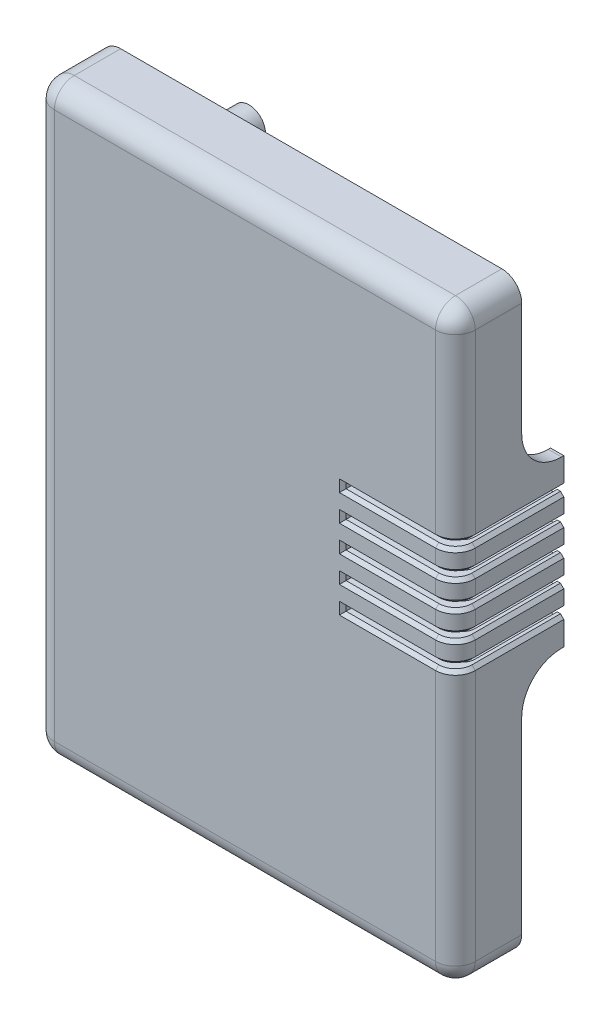
SolidWorks part; units mm, degrees
ref_plane "Front Plane" through (0, 0, 0) normal (0, 0, 1) x (1, 0, 0)
ref_plane "Top Plane" through (0, 0, 0) normal (0, 1, 0) x (1, 0, 0)
ref_plane "Right Plane" through (0, 0, 0) normal (1, 0, 0) x (0, 0, -1)
ref_plane "Plane1" through (0, 0, 8) normal (0, 0, 1) x (1, 0, 0)
sketch "Sketch2" plane through (0, 0, 8) normal (0, 0, 1) x (1, 0, 0)
  line L1 (-23.6788, 60.2968) -> (39.8212, 60.2968)
  line L2 (-23.6788, 60.2968) -> (-23.6788, -28.2032)
  line L3 (-23.6788, -28.2032) -> (39.8212, -28.2032)
  line L4 (39.8212, 60.2968) -> (39.8212, -28.2032)
extrude "Boss-Extrude1" add sketch "Sketch2" along normal blind 2
sketch "Sketch3" plane through (0, 0, 8) normal (0, 0, -1) x (-1, 0, 0)
  line L4 (23.6788, -28.2032) -> (23.6788, 60.2968)
  line L5 (23.6788, 60.2968) -> (-39.8212, 60.2968)
  line L6 (-39.8212, 60.2968) -> (-39.8212, -28.2032)
  line L7 (-39.8212, -28.2032) -> (23.6788, -28.2032)
  line L8 (23.6788, -28.2032) -> (23.6788, 60.2968)
  line L9 (23.6788, 60.2968) -> (-39.8212, 60.2968)
  line L10 (-37.8212, -26.2032) -> (-39.8212, -26.2032)
  line L11 (-39.8212, -28.2032) -> (23.6788, -28.2032)
  line L12 (-39.8212, -28.2032) -> (-39.8212, 60.2968) construction
  line L13 (-39.8212, -26.2032) -> (-39.8212, -28.2032)
  line L14 (-37.8212, 58.2968) -> (-39.8212, 58.2968)
  line L15 (-39.8212, 58.2968) -> (-39.8212, 60.2968)
  line L16 (21.6788, -26.2032) -> (21.6788, 58.2968)
  line L17 (21.6788, 58.2968) -> (-37.8212, 58.2968)
  line L18 (-37.8212, 58.2968) -> (-37.8212, -26.2032)
  line L19 (-37.8212, -26.2032) -> (21.6788, -26.2032)
  line L20 (21.6788, -26.2032) -> (21.6788, 58.2968)
  line L21 (21.6788, 58.2968) -> (-37.8212, 58.2968)
  line L23 (-37.8212, -26.2032) -> (21.6788, -26.2032)
  dimension "D1" = 0
  dimension "D2" = 2
extrude "Boss-Extrude2" add sketch "Sketch3" along normal up to surface (8 mm away) up to face at (-23.6788, 16.0468, 9)
sketch "Sketch4" plane through (39.8212, 0, 0) normal (1, 0, 0) x (0, 0, -1)
  line L0 (0, 40.207) -> (0, 57.2968) construction
  line L1 (6, 9.207) -> (6.35, 9.207) construction
  line L2 (6.35, 34.207) -> (6, 34.207) construction
  line L3 (6.35, 9.207) -> (6.35, 34.207) construction
  line L4 (0, -26.2032) -> (0, 58.2968) construction
  line L5 (0, -26.2032) -> (-8, -26.2032) construction
  line L6 (-8, -26.2032) -> (-8, 58.2968) construction
  line L7 (0, 58.2968) -> (-8, 58.2968) construction
  line L8 (0, 40.207) -> (0, 58.2968)
  line L9 (6, 9.207) -> (6.35, 9.207)
  line L10 (6.35, 34.207) -> (6, 34.207)
  line L11 (6.35, 9.207) -> (6.35, 34.207)
  line L12 (0, -26.2032) -> (0, 3.207)
  line L13 (0, -26.2032) -> (-8, -26.2032)
  line L14 (-8, -26.2032) -> (-8, 58.2968)
  line L15 (0, 58.2968) -> (-8, 58.2968)
  line L16 (0, 40.207) -> (0, 58.2968)
  arc A0 (0, 40.207) -> (6, 34.207) centre (6, 40.207) ccw construction
  arc A1 (6, 9.207) -> (0, 3.207) centre (6, 3.207) ccw construction
  arc A2 (0, 40.207) -> (6, 34.207) centre (6, 40.207) ccw
  arc A3 (6, 9.207) -> (0, 3.207) centre (6, 3.207) ccw
  line M3 (0, -26.2032) -> (-8, -26.2032)
  line M4 (-8, -26.2032) -> (-8, 58.2968)
  line M5 (-8, 58.2968) -> (0, 58.2968)
extrude "Boss-Extrude3" add sketch "Sketch4" against normal blind 2 contours A3 L9 L11 L10 A2 L8 L12 M5 M4 M3 region at (39.8212, 17.2065, 2.5632)
sketch "Sketch5" plane through (0, 0, 8) normal (0, 0, -1) x (-1, 0, 0)
  line L0 (-37.8212, -26.2032) -> (-37.8212, 58.2968) construction
  line L1 (-37.8212, 32.707) -> (-22.8212, 32.707)
  line L2 (-37.8212, 32.707) -> (-37.8212, 30.707)
  line L3 (-37.8212, 30.707) -> (-22.8212, 30.707)
  line L4 (-22.8212, 32.707) -> (-22.8212, 30.707)
  line L5 (-37.8212, 9.207) -> (-37.8212, 34.207) construction
  line L6 (-37.8212, 28.707) -> (-22.8212, 28.707)
  line L7 (-37.8212, 28.707) -> (-37.8212, 26.707)
  line L8 (-37.8212, 26.707) -> (-22.8212, 26.707)
  line L9 (-22.8212, 28.707) -> (-22.8212, 26.707)
  line L10 (-37.8212, 24.707) -> (-22.8212, 24.707)
  line L11 (-37.8212, 24.707) -> (-37.8212, 22.707)
  line L12 (-37.8212, 22.707) -> (-22.8212, 22.707)
  line L13 (-22.8212, 24.707) -> (-22.8212, 22.707)
  line L14 (-37.8212, 20.707) -> (-22.8212, 20.707)
  line L15 (-37.8212, 20.707) -> (-37.8212, 18.707)
  line L16 (-37.8212, 18.707) -> (-22.8212, 18.707)
  line L17 (-22.8212, 20.707) -> (-22.8212, 18.707)
  line L18 (-37.8212, 16.707) -> (-22.8212, 16.707)
  line L19 (-37.8212, 16.707) -> (-37.8212, 14.707)
  line L20 (-37.8212, 14.707) -> (-22.8212, 14.707)
  line L21 (-22.8212, 16.707) -> (-22.8212, 14.707)
  line L22 (-37.8212, 12.707) -> (-22.8212, 12.707)
  line L23 (-37.8212, 12.707) -> (-37.8212, 10.707)
  line L24 (-37.8212, 10.707) -> (-22.8212, 10.707)
  line L25 (-22.8212, 12.707) -> (-22.8212, 10.707)
  line L26 (-37.8212, 22.707) -> (-37.8212, 20.707) construction
  line L28 (-39.8212, 9.207) -> (-39.8212, 34.207) construction
  point P29 (-37.8212, 21.707)
  point P32 (-39.8212, 21.707)
  dimension "D1" = 15
  dimension "D2" = 2
  dimension "D3" = 2
  dimension "D4" = 2
  dimension "D5" = 2
  dimension "D6" = 2
  dimension "D7" = 2
extrude "Boss-Extrude4" add sketch "Sketch5" along normal blind 12
sketch "Sketch6" plane through (0, 0, -6.35) normal (0, 0, -1) x (-1, 0, 0)
  line L0 (-22.8212, 28.707) -> (-37.8212, 28.707) construction
  line L1 (-37.8212, 30.707) -> (-38.8212, 30.707)
  line L2 (-37.8212, 30.707) -> (-37.8212, 28.707)
  line L3 (-37.8212, 28.707) -> (-38.8212, 28.707)
  line L4 (-38.8212, 30.707) -> (-38.8212, 30.107)
  line L5 (-39.8212, 9.207) -> (-39.8212, 34.207) construction
  line L6 (-38.8212, 29.307) -> (-38.8212, 28.707)
  line L7 (-38.8212, 30.107) -> (-39.8212, 30.107)
  line L8 (-38.8212, 26.107) -> (-39.8212, 26.107)
  line L9 (-38.8212, 29.307) -> (-39.8212, 29.307)
  line L10 (-39.8212, 30.107) -> (-39.8212, 29.307)
  line L11 (-38.8212, 26.707) -> (-38.8212, 26.107)
  line L12 (-37.8212, 26.707) -> (-38.8212, 26.707)
  line L13 (-37.8212, 26.707) -> (-37.8212, 24.707)
  line L14 (-37.8212, 24.707) -> (-38.8212, 24.707)
  line L15 (-38.8212, 25.307) -> (-38.8212, 24.707)
  line L16 (-38.8212, 25.307) -> (-39.8212, 25.307)
  line L17 (-39.8212, 26.107) -> (-39.8212, 25.307)
  line L18 (-38.8212, 22.107) -> (-39.8212, 22.107)
  line L19 (-38.8212, 22.707) -> (-38.8212, 22.107)
  line L20 (-37.8212, 22.707) -> (-38.8212, 22.707)
  line L21 (-37.8212, 22.707) -> (-37.8212, 20.707)
  line L22 (-37.8212, 20.707) -> (-38.8212, 20.707)
  line L23 (-38.8212, 21.307) -> (-38.8212, 20.707)
  line L24 (-38.8212, 21.307) -> (-39.8212, 21.307)
  line L25 (-39.8212, 22.107) -> (-39.8212, 21.307)
  line L26 (-38.8212, 18.107) -> (-39.8212, 18.107)
  line L27 (-38.8212, 18.707) -> (-38.8212, 18.107)
  line L28 (-37.8212, 18.707) -> (-38.8212, 18.707)
  line L29 (-37.8212, 18.707) -> (-37.8212, 16.707)
  line L30 (-37.8212, 16.707) -> (-38.8212, 16.707)
  line L31 (-38.8212, 17.307) -> (-38.8212, 16.707)
  line L32 (-38.8212, 17.307) -> (-39.8212, 17.307)
  line L33 (-39.8212, 18.107) -> (-39.8212, 17.307)
  line L34 (-38.8212, 14.107) -> (-39.8212, 14.107)
  line L35 (-38.8212, 14.707) -> (-38.8212, 14.107)
  line L36 (-37.8212, 14.707) -> (-38.8212, 14.707)
  line L37 (-37.8212, 14.707) -> (-37.8212, 12.707)
  line L38 (-37.8212, 12.707) -> (-38.8212, 12.707)
  line L39 (-38.8212, 13.307) -> (-38.8212, 12.707)
  line L40 (-38.8212, 13.307) -> (-39.8212, 13.307)
  line L41 (-39.8212, 14.107) -> (-39.8212, 13.307)
  point P13 (-39.8212, 29.707)
  point P14 (-37.8212, 29.707)
  dimension "D1" = 1
  dimension "D2" = 0.8
  dimension "D3" = 5
extrude "Cut-Extrude1" cut sketch "Sketch6" against normal up to surface (14.35 mm away) up to face at (27.1427, 20.8984, 8)
fillet "Fillet1" radius 3 4 edges at (-23.6788, 16.0468, 10) (8.0712, -28.2032, 10) (8.0712, 60.2968, 10) (39.8212, 16.0468, 10)
fillet "Fillet2" radius 2 15 edges at (8.0712, -26.2032, 8) (37.8212, -7.7481, 8) (-21.6788, 16.0468, 8) (8.0712, 58.2968, 8) (37.8212, 45.5019, 8) (38.8212, 13.007, 8) (38.8212, 14.407, 8) (38.8212, 17.007, 8) (38.8212, 18.407, 8) (38.8212, 21.007, 8) (38.8212, 22.407, 8) (38.8212, 25.007, 8) (38.8212, 26.407, 8) (38.8212, 29.007, 8) (38.8212, 30.407, 8)
fillet "Fillet3" radius 3 8 edges at (38.9426, 59.4181, 9.1213) (-22.8001, 59.4181, 9.1213) (-22.8001, -27.3245, 9.1213) (38.9426, -27.3245, 9.1213) (39.8212, 60.2968, 3.5) (-23.6788, 60.2968, 3.5) (-23.6788, -28.2032, 3.5) (39.8212, -28.2032, 3.5)
sketch "Sketch7" plane through (0, 0, 8) normal (0, 0, -1) x (-1, 0, 0)
  line L0 (-22.8212, 30.707) -> (-22.8212, 32.707) construction
  line L1 (-39.6497, 30.107) -> (-22.8212, 30.107)
  line L2 (-39.6497, 30.107) -> (-39.6497, 29.307)
  line L3 (-39.6497, 29.307) -> (-22.8212, 29.307)
  line L4 (-22.8212, 30.107) -> (-22.8212, 29.307)
  line L5 (-39.6497, 26.107) -> (-39.6497, 25.307)
  line L6 (-39.6497, 26.107) -> (-22.8212, 26.107)
  line L7 (-39.6497, 25.307) -> (-22.8212, 25.307)
  line L8 (-22.8212, 26.107) -> (-22.8212, 25.307)
  line L9 (-39.6497, 22.107) -> (-39.6497, 21.307)
  line L10 (-39.6497, 22.107) -> (-22.8212, 22.107)
  line L11 (-39.6497, 21.307) -> (-22.8212, 21.307)
  line L12 (-22.8212, 22.107) -> (-22.8212, 21.307)
  line L13 (-39.6497, 18.107) -> (-39.6497, 17.307)
  line L14 (-39.6497, 18.107) -> (-22.8212, 18.107)
  line L15 (-39.6497, 17.307) -> (-22.8212, 17.307)
  line L16 (-22.8212, 18.107) -> (-22.8212, 17.307)
  line L17 (-39.6497, 14.107) -> (-39.6497, 13.307)
  line L18 (-39.6497, 14.107) -> (-22.8212, 14.107)
  line L19 (-39.6497, 13.307) -> (-22.8212, 13.307)
  line L20 (-22.8212, 14.107) -> (-22.8212, 13.307)
  dimension "D1" = 5
extrude "Cut-Extrude2" cut sketch "Sketch7" against normal blind 10
sketch "Sketch8" plane through (0, -28.2032, 0) normal (0, -1, 0) x (1, 0, 0)
  line L0 (-20.6788, 0) -> (36.8212, 0) construction
  line L1 (13.7903, 0) -> (-13.0098, 0)
  line L2 (13.7903, 0) -> (13.7903, 7)
  line L3 (13.7903, 7) -> (-13.0098, 7)
  line L4 (-13.0098, 0) -> (-13.0098, 7)
  line L5 (13.7903, -6.35) -> (13.7903, 0) construction
  line L6 (-13.0098, 0) -> (-13.0098, -6.35) construction
  line L8 (36.8212, 7) -> (-20.6788, 7) construction
  point P8 (13.7903, 10)
  point P11 (13.7903, 7)
sketch "Sketch9" plane through (0, 0, 8) normal (0, 0, -1) x (-1, 0, 0)
  circle A0 centre (15.6788, -20.7032) radius 2.5
  circle A1 centre (-32.3212, 5.2968) radius 2.5
  circle A2 centre (7.6788, 53.7968) radius 2.5
  point P9 (0, 0)
  point P10 (0, 0)
  point P11 (0, 0)
  dimension "D1" = 5
  dimension "D2" = 5
  dimension "D3" = 5
extrude "Boss-Extrude5" add sketch "Sketch9" along normal up to surface (14.35 mm away)
sketch "Sketch11" plane through (0, 0, -6.35) normal (0, 0, -1) x (-1, 0, 0)
  line L0 (7.6788, 51.2968) -> (7.6788, 56.2968) construction
  line L1 (5.1788, 53.7968) -> (10.1788, 53.7968) construction
  circle A0 centre (7.6788, 53.7968) radius 2.5 construction
  point P7 (7.6788, 53.7968)
ref_plane "Plane2" through (-7.6788, 0, 0) normal (-1, 0, 0) x (0, 0, 1)
sketch "Sketch13" plane through (-7.6788, 0, 0) normal (-1, 0, 0) x (0, 0, 1)
  line L0 (8, 48.1691) -> (-1, 51.2968)
  line L1 (8, 56.2968) -> (8, 32.707) construction
  line L2 (-6.35, 51.2968) -> (8, 51.2968) construction
  line L4 (8, -24.2032) -> (8, 56.2968) construction
  line L5 (8, 48.1691) -> (8, 58.2968)
  line L6 (8, 58.2968) -> (-1, 58.2968)
  line L7 (-1, 58.2968) -> (-1, 51.2968)
  line L8 (0, 58.2968) -> (6, 58.2968) construction
  dimension "D1" = 9
extrude "Boss-Extrude6" add sketch "Sketch13" along normal mid plane 1
ref_plane "Plane3" through (0, 53.7968, 0) normal (0, 1, 0) x (1, 0, 0)
sketch "Sketch14" plane through (0, 53.7968, 0) normal (0, 1, 0) x (1, 0, 0)
  line L0 (-10.1788, 1) -> (-12.7549, -8)
  line L1 (-10.1788, 6.35) -> (-10.1788, -8) construction
  line L2 (-19.6788, -8) -> (-8.1788, -8) construction
  line L3 (-12.7549, -8) -> (-2.6026, -8)
  line L4 (-8.1788, -8) -> (-7.1788, -8) construction
  line L5 (-10.1788, 1) -> (-5.1788, 1)
  line L6 (-8.1788, 1) -> (-7.1788, 1) construction
  line L7 (-7.6788, 1) -> (-7.6788, -8) construction
  line L8 (-5.1788, 1) -> (-2.6026, -8)
extrude "Boss-Extrude7" add sketch "Sketch14" along normal mid plane 1
sketch "Sketch15" plane through (0, 0, -6.35) normal (0, 0, -1) x (-1, 0, 0)
  line L0 (15.6788, -23.2032) -> (15.6788, -18.2032) construction
  line L1 (13.1788, -20.7032) -> (18.1788, -20.7032) construction
  circle A0 centre (15.6788, -20.7032) radius 2.5 construction
  point P7 (15.6788, -20.7032)
ref_plane "Plane4" through (-15.6788, 0, 0) normal (-1, 0, 0) x (0, 0, 1)
sketch "Sketch16" plane through (-15.6788, 0, 0) normal (-1, 0, 0) x (0, 0, 1)
  line L0 (0, -26.2032) -> (8, -26.2032)
  line L1 (8, -26.2032) -> (8, -14.2683)
  line L2 (8, -24.2032) -> (8, 56.2968) construction
  line L3 (8, -14.2683) -> (-1, -18.2032)
  line L4 (8, -18.2032) -> (-6.35, -18.2032) construction
  line L5 (-1, -18.2032) -> (-1, -26.2032)
  line L6 (-1, -26.2032) -> (0, -26.2032)
  dimension "D1" = 9
extrude "Boss-Extrude8" add sketch "Sketch16" along normal mid plane 1
ref_plane "Plane5" through (0, -20.7032, 0) normal (0, -1, 0) x (-1, 0, 0)
sketch "Sketch17" plane through (0, -20.7032, 0) normal (0, -1, 0) x (-1, 0, 0)
  line L1 (16.1788, 1) -> (21.6788, 1)
  line L2 (16.1788, 1) -> (16.1788, -8)
  line L3 (16.1788, -8) -> (21.6788, -8)
  line L4 (21.6788, 1) -> (21.6788, -8)
  line L5 (21.6788, 0) -> (21.6788, -6) construction
  line L6 (16.1788, 1) -> (15.1788, 1) construction
  line L7 (16.1788, -8) -> (19.6788, -8) construction
extrude "Boss-Extrude11" add sketch "Sketch17" along normal mid plane 1
sketch "Sketch18" plane through (0, 0, -6.35) normal (0, 0, -1) x (-1, 0, 0)
  line L0 (-32.3212, 7.7968) -> (-32.3212, 2.7968) construction
  line L1 (-34.8212, 5.2968) -> (-29.8212, 5.2968) construction
  circle A0 centre (-32.3212, 5.2968) radius 2.5 construction
  point P7 (-32.3212, 5.2968)
ref_plane "Plane6" through (32.3212, 0, 0) normal (1, 0, 0) x (0, 0, -1)
sketch "Sketch19" plane through (32.3212, 0, 0) normal (1, 0, 0) x (0, 0, -1)
  line L0 (1, 2.7968) -> (-8, -0.4734)
  line L1 (-8, 2.7968) -> (6.35, 2.7968) construction
  line L2 (-8, 10.707) -> (-8, -24.2032) construction
  line L3 (-8, -0.4734) -> (-8, 11.707)
  line L4 (-8, 10.707) -> (-8, 12.707) construction
  line L5 (-8, 11.707) -> (1, 11.707)
  line L6 (1, 11.707) -> (1, 2.7968)
  dimension "D1" = 9
extrude "Boss-Extrude12" add sketch "Sketch19" along normal mid plane 1
ref_plane "Plane7" through (0, 5.2968, 0) normal (0, -1, 0) x (-1, 0, 0)
sketch "Sketch20" plane through (0, 5.2968, 0) normal (0, -1, 0) x (-1, 0, 0)
  line L0 (-37.8212, 1) -> (-29.8212, 1)
  line L2 (-29.8212, -8) -> (-29.8212, 6.35) construction
  line L3 (-29.8212, 1) -> (-26.3307, -8)
  line L4 (-35.8212, -8) -> (15.1788, -8) construction
  line L5 (-26.3307, -8) -> (-37.8212, -8)
  line L6 (-37.8212, -8) -> (-37.8212, 1)
  line L7 (-32.8212, 1) -> (-32.3212, 1) construction
  line L8 (-22.8212, -8) -> (-36.8212, -8) construction
  line L9 (-37.8212, 0) -> (-37.8212, 6) construction
extrude "Boss-Extrude13" add sketch "Sketch20" along normal mid plane 1
hole_wizard "M2.5 Clearance Hole1" positions "3DSketch3" profile "Sketch23" hole size "M2.5" standard "ISO"
sketch3d "3DSketch3"
  point P0 (32.3212, 5.2968, -6.35)
  point P3 (-7.6788, 53.7968, -6.35)
  point P6 (-15.6788, -20.7032, -6.35)
sketch "Sketch23" plane through (32.3212, 5.2968, -6.35) normal (1, 0, 0) x (0, 1, 0)
  line L0 (0, 0) -> (0, 10.8712)
  line L1 (0, 10.8712) -> (1.45, 10)
  line L2 (1.45, 10) -> (1.45, 0)
  line L5 (1.45, 0) -> (0, 0)
  line L10 (0, 10.8712) -> (-1.45, 10) construction
  line L11 (0, -6.35) -> (0, 107.95) construction
  dimension "Hole Dia." = 2.9
  dimension "Hole Depth" = 10
  dimension "Drill Angle" = 118
extrude "Cut-Extrude3" cut sketch "Sketch8" against normal blind 3
chamfer "Chamfer1" distance 0.5 angle 45 35 edges at (39.8212, 13.307, 0.325) (39.8212, 14.107, 0.325) (38.9426, 13.307, 9.1213) (38.9426, 14.107, 9.1213) (29.8212, 13.307, 10) (22.8212, 13.707, 10) (29.8212, 14.107, 10) (39.8212, 17.307, 0.325) (39.8212, 18.107, 0.325) (38.9426, 17.307, 9.1213) (38.9426, 18.107, 9.1213) (29.8212, 17.307, 10) (29.8212, 18.107, 10) (22.8212, 17.707, 10) (22.8212, 21.707, 10) (29.8212, 21.307, 10) (39.8212, 21.307, 0.325) (38.9426, 21.307, 9.1213) (39.8212, 22.107, 0.325) (29.8212, 22.107, 10) (38.9426, 22.107, 9.1213) (39.8212, 25.307, 0.325) (39.8212, 26.107, 0.325) (38.9426, 25.307, 9.1213) (38.9426, 26.107, 9.1213) (29.8212, 25.307, 10) (29.8212, 26.107, 10) (22.8212, 25.707, 10) (29.8212, 29.307, 10) (39.8212, 29.307, 0.325) (38.9426, 29.307, 9.1213) (39.8212, 30.107, 0.325) (38.9426, 30.107, 9.1213) (22.8212, 29.707, 10) (29.8212, 30.107, 10)
